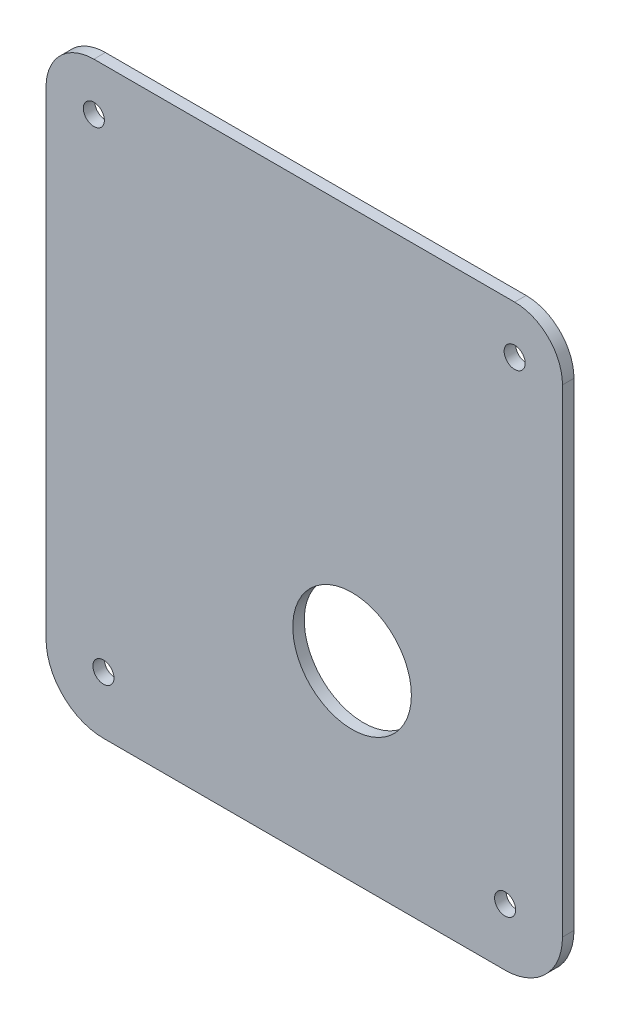
SolidWorks part; units mm, degrees
note: '?' marks a value the reader was unsure of.
other "Title Block Table1"
other "DetailItem1"
material "6082-T6 Aluminium"
ref_plane "Front Plane" through (0, 0, 0) normal (0, 0, 1) x (1, 0, 0)
ref_plane "Top Plane" through (0, 0, 0) normal (0, 1, 0) x (1, 0, 0)
ref_plane "Right Plane" through (0, 0, 0) normal (1, 0, 0) x (0, 0, -1)
ref_axis "X-Axis" through (-87.25, 0, 0) along (1, 0, 0)?
ref_axis "Y-Axis" through (0, 120.625, 0) along (0, -1, 0)?
ref_axis "Z-Axis" through (0, 0, -0.15) along (0, 0, 1)?
sketch "Sketch1" plane through (0, 0, 0) normal (0, 0, 1) x (1, 0, 0)
  line L0 (0, 0) -> (0, -50) construction
  line L2 (-80, 90) -> (-80, -50) construction
  line L3 (-80, -50) -> (80, -50) construction
  line L5 (-67.5, 102.5) -> (42.5, 102.5)
  line L6 (55, 90) -> (55, -35)
  line L8 (40, -50) -> (-65, -50)
  line L9 (-80, -35) -> (-80, 90)
  arc A0 (-67.5, 102.5) -> (-80, 90) centre (-67.5, 90) ccw
  arc A1 (55, -35) -> (40, -50) centre (40, -35) cw
  arc A2 (-65, -50) -> (-80, -35) centre (-65, -35) cw
  arc A3 (42.5, 102.5) -> (55, 90) centre (42.5, 90) cw
  point P0 (0, 0)
  dimension "D5" = 15
  dimension "D1" = 12.5
  dimension "D2" = 140
  dimension "D3" = 50
  dimension "D4" = 120
  dimension "D6" = 80
base flange "Base-Flange1" sketch "Sketch1" thickness 3 reverse thickness direction yes parameters "D1"=3
sketch "Sketch2" plane through (0, 0, 3) normal (0, 0, 1) x (1, 0, 0)
  circle A0 centre (0, 0) radius 15.5
  dimension "D1" = 31
extrude "Cut-Extrude1" cut sketch "Sketch2" against normal through all normal cut yes
hole_wizard "M5 Clearance Hole1" positions "Sketch3" profile "Sketch5" hole size "M5" standard "DIN" end condition through all
sketch "Sketch3" plane through (0, 0, 0) normal (0, 0, -1) x (-1, 0, 0)
  point P0 (-40, -35)
  point P3 (67.5, 90)
  point P6 (65, -35)
  point P11 (-42.5, 90)
sketch "Sketch5" plane through (40, -35, 0) normal (1, 0, 0) x (0, 1, 0)
  line L0 (0, 0) -> (0, 3)
  line L1 (0, 3) -> (2.75, 3)
  line L2 (2.75, 3) -> (2.75, 0)
  line L5 (2.75, 0) -> (0, 0)
  line L11 (0, -6.35) -> (0, 107.95) construction
  dimension "Thru Hole Dia." = 5.5
  dimension "Thru Hole Depth" = 3
sketch "Bend-Lines1" [suppressed] plane through (0, 0, 0) normal (0, 1, 0) x (1, 0, 0)
sketch "Bounding-Box1" [suppressed] plane through (0, 0, 0) normal (0, 1, 0) x (1, 0, 0)
sheet metal parameters "Sheet-Metal3" thickness 3 parameters "D1"=5
flat pattern "Flat-Pattern3" [suppressed]
sketch "Bend-Lines2" plane through (0, 0, 0) normal (0, 1, 0) x (1, 0, 0)
sketch3d "Bounding-Box2" [suppressed]
  line L0 (-73.324, -72.775, 0) -> (73.324, -72.775, 0) construction
  line L1 (-73.324, 72.775, 0) -> (73.324, 72.775, 0) construction
  line L2 (-73.324, -72.775, 0) -> (-73.324, 72.775, 0) construction
  line L3 (73.324, -72.775, 0) -> (73.324, 72.775, 0) construction
sheet metal parameters "Sheet-Metal4" thickness 3 parameters "D1"=5
flat pattern "Flat-Pattern3"
sketch "Bend-Lines2" plane through (0, 0, 0) normal (0, 1, 0) x (1, 0, 0)
sketch3d "Bounding-Box2" [suppressed]
  line L0 (-12.5, 196.7647, 0) -> (-12.5, -12.5, 0) construction
  line L1 (111.2472, 196.7647, 0) -> (111.2472, -12.5, 0) construction
  line L2 (-12.5, 196.7647, 0) -> (111.2472, 196.7647, 0) construction
  line L3 (-12.5, -12.5, 0) -> (111.2472, -12.5, 0) construction
sheet metal parameters "Sheet-Metal5" thickness 3 parameters "D1"=5
flat pattern "Flat-Pattern3"
sketch "Bend-Lines2" plane through (0, 0, 0) normal (0, 1, 0) x (1, 0, 0)
sketch3d "Bounding-Box2" [suppressed]
  line L0 (-12.5, -140, 0) -> (-12.5, 12.5, 0) construction
  line L1 (122.5, -140, 0) -> (122.5, 12.5, 0) construction
  line L2 (-12.5, -140, 0) -> (122.5, -140, 0) construction
  line L3 (-12.5, 12.5, 0) -> (122.5, 12.5, 0) construction
